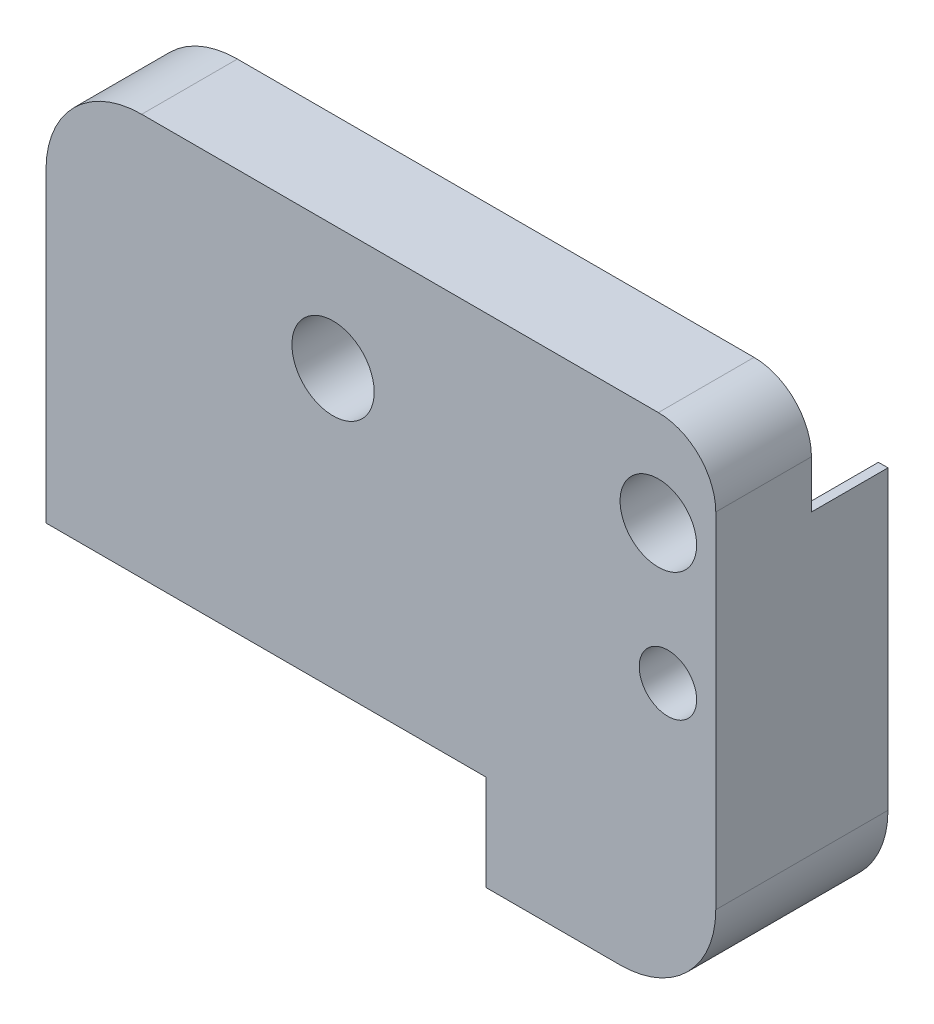
SolidWorks part; units mm, degrees
ref_plane "Front" through (0, 0, 0) normal (0, 0, 1) x (1, 0, 0)
ref_plane "Top" through (0, 0, 0) normal (0, 1, 0) x (1, 0, 0)
ref_plane "Right" through (0, 0, 0) normal (1, 0, 0) x (0, 0, -1)
sketch "Sketch1" plane through (0, 0, 0) normal (0, 0, 1) x (1, 0, 0)
  line L1 (-15, 6.5) -> (8, 6.5)
  line L2 (-15, 6.5) -> (-15, -14.5)
  line L3 (-15, -14.5) -> (8, -14.5)
  line L4 (8, 6.5) -> (8, -14.5)
  dimension "D1" = 15
  dimension "D2" = 14.5
  dimension "D3" = 6.5
  dimension "D4" = 8
extrude "Extrude1" add sketch "Sketch1" along normal blind 5
sketch "Sketch2" plane through (0, 0, 5) normal (0, 0, 1) x (1, 0, 0)
  circle A0 centre (0, 0) radius 2.15
  dimension "D1" = 4.3
extrude "Extrude2" cut sketch "Sketch2" against normal blind 4.3
sketch "Sketch3" plane through (0, 0, 0) normal (0, 0, -1) x (-1, 0, 0)
  line L1 (15, -14.5) -> (-8, -14.5) construction
  line L2 (-8, -14.5) -> (-8, 6.5) construction
  circle A0 centre (4.9, -6.5) radius 4.5
  dimension "D1" = 9
  dimension "D3" = 8
  dimension "D2" = 12.9
extrude "Extrude3" cut sketch "Sketch3" against normal blind 4.5
sketch "Sketch4" plane through (0, -14.5, 0) normal (0, -1, 0) x (1, 0, 0)
  line L0 (8, 5) -> (8, 0) construction
  line L1 (-15, 5) -> (-15, 0) construction
  line L2 (-15, 0) -> (8, 0) construction
  circle A0 centre (-12, 2.5) radius 1.25
  circle A1 centre (1.4, 2.5) radius 1.25
  dimension "D1" = 2.5
  dimension "D2" = 2.5
  dimension "D4" = 3
  dimension "D5" = 2.5
  dimension "D6" = 2.5
  dimension "D3" = 6.6
extrude "Extrude4" cut sketch "Sketch4" against normal blind 8
cosmetic thread "Hole Thread1" parameters "D1"=6, "D2"=3
cosmetic thread "Hole Thread2" parameters "D1"=6, "D2"=3
sketch "Sketch7" plane through (0, 0, 5) normal (0, 0, 1) x (1, 0, 0)
  line L0 (-15, -14.5) -> (8, -14.5) construction
  line L1 (8, 6.5) -> (20, 6.5)
  line L2 (8, 6.5) -> (8, -19.5)
  line L3 (8, -19.5) -> (20, -19.5)
  line L4 (20, 6.5) -> (20, -19.5)
  dimension "D1" = 12
  dimension "D2" = 5
extrude "Extrude6" add sketch "Sketch7" against normal up to surface (5 mm away) up to face at (-9.4, -6.5, 0)
sketch "Sketch8" plane through (0, 0, 5) normal (0, 0, 1) x (1, 0, 0)
  line L0 (20, -19.5) -> (20, 6.5) construction
  line L1 (20, 6.5) -> (-15, 6.5) construction
  circle A0 centre (17, 1.5) radius 2
  dimension "D1" = 4
  dimension "D3" = 5
  dimension "D2" = 3
extrude "Extrude7" cut sketch "Sketch8" against normal blind 4
sketch "Sketch9" plane through (0, 0, 5) normal (0, 0, 1) x (1, 0, 0)
  line L0 (20, -19.5) -> (20, 6.5) construction
  line L3 (-15, -14.5) -> (8, -14.5) construction
  circle A0 centre (17.5, -5.5) radius 1.5
  dimension "D1" = 3
  dimension "D3" = 9
  dimension "D2" = 2.5
extrude "Extrude8" cut sketch "Sketch9" against normal up to surface (5 mm away) up to face at (-9.4, -6.5, 0)
fillet "Fillet2" radius 3 2 edges at (20, -19.5, 2.5) (20, 6.5, 2.5)
hole_wizard "M3 Tapped Hole1" positions "3DSketch1" profile "Sketch10" tap size "M3" standard "DIN"
sketch3d "3DSketch1"
  line L0 (-12, -6.5, 2.5) -> (-12, -14.5, 2.5) construction
  line L1 (1.4, -6.5, 2.5) -> (1.4, -14.5, 2.5) construction
  point P0 (-12, -14.5, 2.5)
  point P4 (1.4, -14.5, 2.5)
sketch "Sketch10" plane through (-12, -14.5, 2.5) normal (1, 0, 0) x (0, 0, -1)
  line L0 (0, 0) -> (0, 8.7511)
  line L1 (0, 8.7511) -> (1.25, 8)
  line L2 (1.25, 8) -> (1.25, 0)
  line L5 (1.25, 0) -> (0, 0)
  line L10 (0, 8.7511) -> (-1.25, 8) construction
  line L11 (0, -6.35) -> (0, 107.95) construction
  dimension "Tap Drill Dia." = 2.5
  dimension "Tap Drill Depth" = 8
  dimension "Drill Angle" = 118
sketch "Sketch11" plane through (0, 0, 0) normal (0, 0, -1) x (-1, 0, 0)
  line L0 (-8, -19.5) -> (-20, -19.5)
  line L1 (-20, -19.5) -> (-20, 1)
  line L2 (-20, 3.5) -> (-20, -16.5) construction
  line L3 (-20, 1) -> (-18.1, 1)
  line L4 (-18.1, 1) -> (-2, -11.07)
  line L5 (-2, -11.07) -> (-2, -14.5)
  line L6 (15, -14.5) -> (-8, -14.5) construction
  line L7 (-2, -14.5) -> (-8, -14.5)
  line L8 (-8, -14.5) -> (-8, -19.5)
  dimension "D1" = 18
  dimension "D2" = 1.9
  dimension "D3" = 8.43
  dimension "D4" = 20.5
extrude "Extrude9" add sketch "Sketch11" along normal blind 4
fillet "Fillet1" radius 5 2 edges at (-15, 6.5, 2.5) (20, -19.5, -2)
sketch "Sketch12" plane through (0, 0, -4) normal (0, 0, -1) x (-1, 0, 0)
  line L0 (-19.5, 1) -> (-19.5, -7.5)
  line L1 (-18.1, 1) -> (-20, 1) construction
  line L2 (-19.5, -7.5) -> (-15.5, -7.5)
  line L3 (-15.5, -7.5) -> (-15.5, -0.9492)
  line L4 (-2, -11.07) -> (-18.1, 1) construction
  line L5 (-15.5, -0.9492) -> (-18.1, 1)
  line L6 (-18.1, 1) -> (-19.5, 1)
  line L7 (-20, 1) -> (-20, -14.5) construction
  dimension "D1" = 4
  dimension "D2" = 0.5
  dimension "D3" = 8.5
extrude "Extrude10" cut sketch "Sketch12" against normal up to surface (4 mm away) up to face at (-9.4, -6.5, 0)
fillet "Fillet3" radius 2 2 edges at (15.5, -7.5, -2) (19.5, -7.5, -2)
